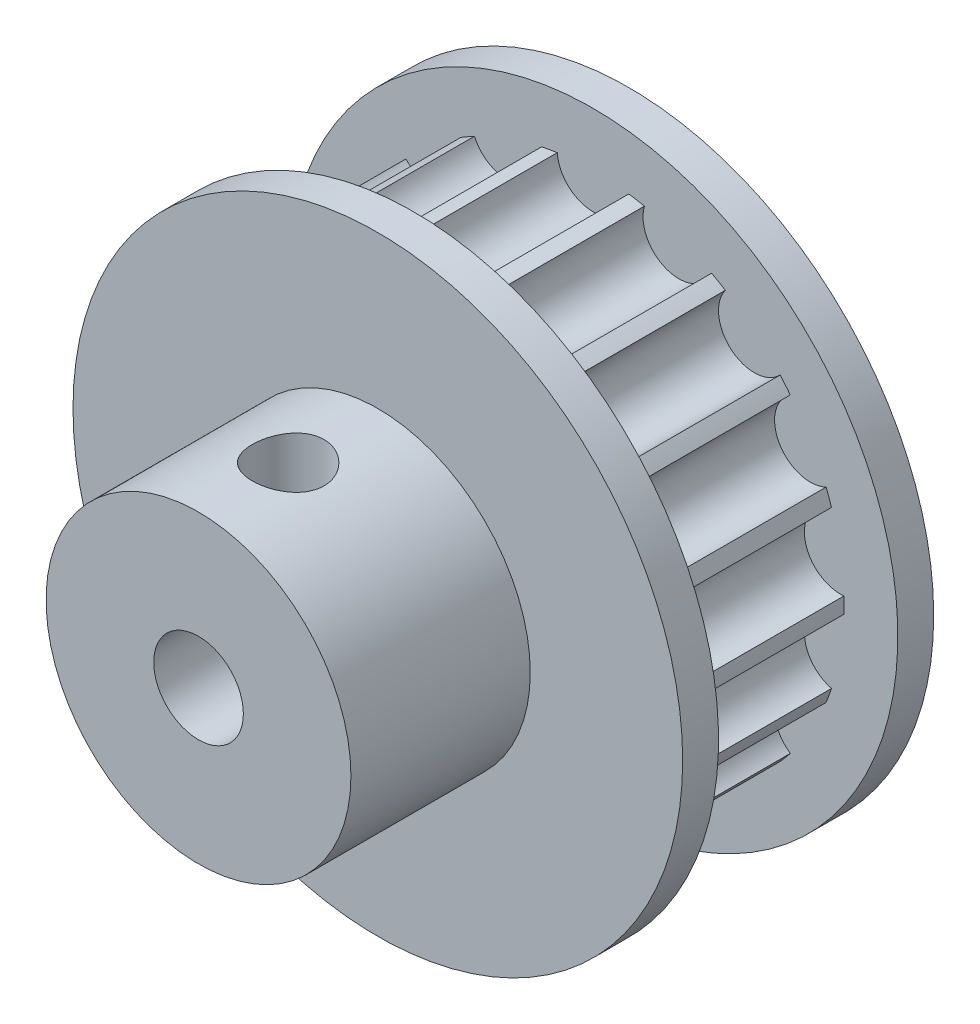
SolidWorks part; units mm, degrees
ref_plane "前视基准面" through (0, 0, 0) normal (0, 0, 1) x (1, 0, 0)
ref_plane "上视基准面" through (0, 0, 0) normal (0, 1, 0) x (1, 0, 0)
ref_plane "右视基准面" through (0, 0, 0) normal (1, 0, 0) x (0, 0, -1)
sketch "Sketch1" plane through (0, 0, 0) normal (0, 0, 1) x (1, 0, 0)
  circle A0 centre (0, 0) radius 17
  dimension "D1" = 34
extrude "Boss-Extrude1" add sketch "Sketch1" along normal blind 14
sketch "Sketch3" plane through (0, 0, 14) normal (0, 0, 1) x (1, 0, 0)
  circle A0 centre (0, 0) radius 2.5
  dimension "D1" = 5
extrude "Cut-Extrude2" cut sketch "Sketch3" against normal up to next
sketch "Sketch5" plane through (0, 0, 14) normal (0, 0, 1) x (1, 0, 0)
  circle A0 centre (0, 0) radius 2.5
  circle A1 centre (0, 0) radius 8.5
  dimension "D1" = 17
extrude "Boss-Extrude2" add sketch "Sketch5" along normal blind 10
sketch "Sketch6" plane through (0, 0, 24) normal (0, 0, 1) x (1, 0, 0)
  line L0 (-1.5691, 2) -> (1.4281, 2) construction
  line L1 (1.5, 2) -> (-1.5, 2)
  arc A0 (1.5, 2) -> (-1.5, 2) centre (0, 0) ccw
  dimension "D1" = 2
ref_plane "Plane1" through (0, 0, 7) normal (0, 0, -1) x (-1, 0, 0)
sketch "Sketch7" plane through (0, 0, 7) normal (0, 0, -1) x (-1, 0, 0)
  circle A0 centre (0, 0) radius 17
  circle A1 centre (0, 0) radius 14
extrude "Cut-Extrude5" cut sketch "Sketch7" against normal mid plane 10
sketch "Sketch8" plane through (0, 0, 7) normal (0, 0, -1) x (-1, 0, 0)
  circle A0 centre (0, 0) radius 14 construction
  circle A1 centre (0, 14) radius 2
  circle A2 centre (4.7883, 13.1557) radius 2
  circle A3 centre (8.999, 10.7246) radius 2
  circle A4 centre (12.1244, 7) radius 2
  circle A5 centre (13.7873, 2.4311) radius 2
  circle A6 centre (13.7873, -2.4311) radius 2
  circle A7 centre (12.1244, -7) radius 2
  circle A8 centre (8.999, -10.7246) radius 2
  circle A9 centre (4.7883, -13.1557) radius 2
  circle A10 centre (0, -14) radius 2
  circle A11 centre (-4.7883, -13.1557) radius 2
  circle A12 centre (-8.999, -10.7246) radius 2
  circle A13 centre (-12.1244, -7) radius 2
  circle A14 centre (-13.7873, -2.4311) radius 2
  circle A15 centre (-13.7873, 2.4311) radius 2
  circle A16 centre (-12.1244, 7) radius 2
  circle A17 centre (-8.999, 10.7246) radius 2
  circle A18 centre (-4.7883, 13.1557) radius 2
  dimension "D1" = 18
  dimension "D2" = 4
extrude "Cut-Extrude6" cut sketch "Sketch8" against normal mid plane 10
sketch "Sketch9" plane through (0, 0, 0) normal (0, 1, 0) x (1, 0, 0)
  circle A0 centre (0, -19) radius 2
extrude "Cut-Extrude7" cut sketch "Sketch9" along normal blind 10
